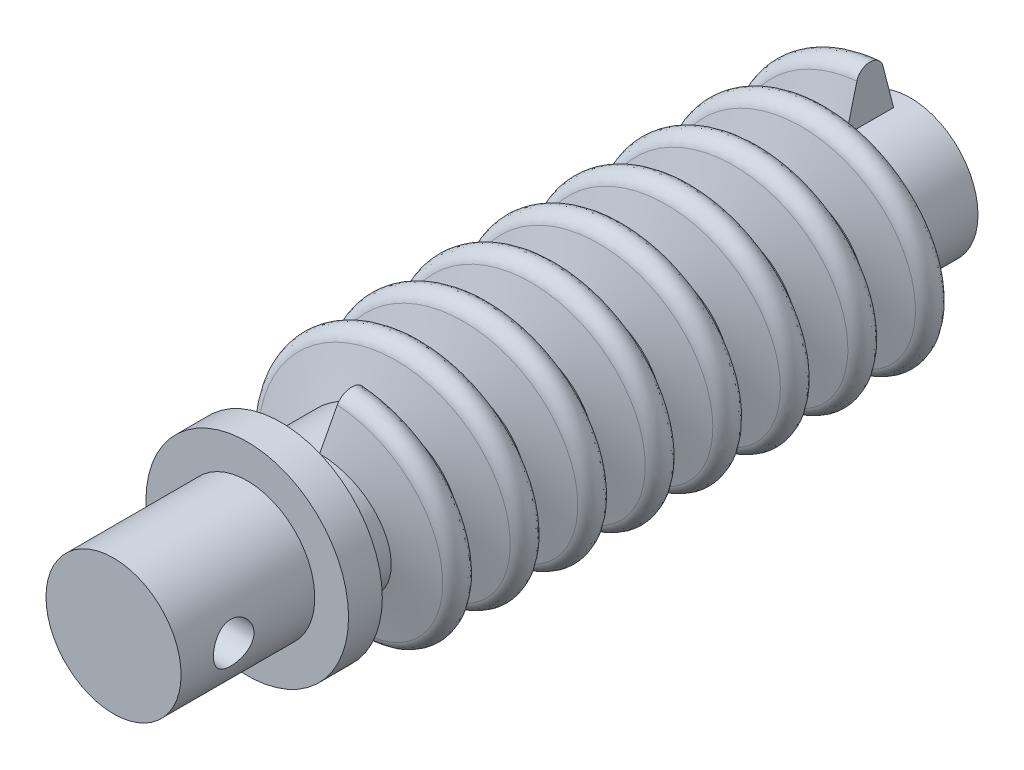
SolidWorks part; units mm, degrees
ref_plane "Front Plane" through (0, 0, 0) normal (0, 0, 1) x (1, 0, 0)
ref_plane "Top Plane" through (0, 0, 0) normal (0, 1, 0) x (1, 0, 0)
ref_plane "Right Plane" through (0, 0, 0) normal (1, 0, 0) x (0, 0, -1)
sketch "Sketch2" plane through (0, 0, 0) normal (0, 0, 1) x (1, 0, 0)
  circle A0 centre (0, 0) radius 5
  dimension "D1" = 10
extrude "Boss-Extrude1" add sketch "Sketch2" along normal blind 38
sketch "Sketch3" plane through (0, 0, 38) normal (0, 0, 1) x (1, 0, 0)
  circle A0 centre (0, 0) radius 5 construction
  circle A1 centre (0, 0) radius 5
curve "Helix/Spiral1" pitch 5 height 40 radius 5 centre (0, 0, 38) axis (0, 0, -1) start towards (0, 1, 0)
sketch "Sketch4" plane through (0, 0, 38) normal (0, 0, 1) x (1, 0, 0)
  circle A1 centre (0, 0) radius 5
  circle A2 centre (0, 0) radius 5
  dimension "D1" = 0
sketch "Sketch6" plane through (0, 0, 38) normal (0, 0, 1) x (1, 0, 0)
  circle A1 centre (0, 0) radius 5
  circle A2 centre (0, 0) radius 5
  dimension "D1" = 0
extrude "Boss-Extrude3" add sketch "Sketch6" along normal blind 16 and the other way blind 43
sketch "Sketch7" plane through (0, 0, 0) normal (1, 0, 0) x (0, 0, -1)
  line L0 (-38, 5) -> (-38, 7.8) construction
  line L1 (5, 5) -> (-54, 5) construction
  line L2 (-39.75, 5) -> (-38.9687, 8.0483)
  line L3 (-36.25, 5) -> (-37.0313, 8.0483)
  line L4 (-39.75, 5) -> (-39.75, 4.2924)
  line L5 (-39.75, 4.2924) -> (-36.25, 4.2924)
  line L6 (-36.25, 4.2924) -> (-36.25, 5)
  arc A0 (-38.9687, 8.0483) -> (-37.0313, 8.0483) centre (-38, 7.8) cw
  spline S0 degree 3 poles (-38, 5) (-37.8965, 5) (-37.6872, 4.7397) (-37.3751, 3.6276) (-37.0625, 1.9632) (-36.75, 0) (-36.4375, -1.9632) (-36.125, -3.6276) (-35.8125, -4.7397) (-35.5, -5.1302) (-35.1875, -4.7397) (-34.875, -3.6276) (-34.4583, -1.4084) (-34.0417, 1.4084) (-33.625, 3.6276) (-33.3125, 4.7397) (-33, 5.1302) (-32.6875, 4.7397) (-32.375, 3.6276) (-31.9583, 1.4084) (-31.5417, -1.4084) (-31.125, -3.6276) (-30.8125, -4.7397) (-30.5, -5.1302) (-30.1875, -4.7397) (-29.875, -3.6276) (-29.4583, -1.4084) (-29.0417, 1.4084) (-28.625, 3.6276) (-28.3125, 4.7397) (-28, 5.1302) (-27.6875, 4.7397) (-27.375, 3.6276) (-26.9583, 1.4084) (-26.5417, -1.4084) (-26.125, -3.6276) (-25.8125, -4.7397) (-25.5, -5.1302) (-25.1875, -4.7397) (-24.875, -3.6276) (-24.4583, -1.4084) (-24.0417, 1.4084) (-23.625, 3.6276) (-23.3125, 4.7397) (-23, 5.1302) (-22.6875, 4.7397) (-22.375, 3.6276) (-21.9583, 1.4084) (-21.5417, -1.4084) (-21.125, -3.6276) (-20.8125, -4.7397) (-20.5, -5.1302) (-20.1875, -4.7397) (-19.875, -3.6276) (-19.4583, -1.4084) (-19.0417, 1.4084) (-18.625, 3.6276) (-18.3125, 4.7397) (-18, 5.1302) (-17.6875, 4.7397) (-17.375, 3.6276) (-16.9583, 1.4084) (-16.5417, -1.4084) (-16.125, -3.6276) (-15.8125, -4.7397) (-15.5, -5.1302) (-15.1875, -4.7397) (-14.875, -3.6276) (-14.4583, -1.4084) (-14.0417, 1.4084) (-13.625, 3.6276) (-13.3125, 4.7397) (-13, 5.1302) (-12.6875, 4.7397) (-12.375, 3.6276) (-11.9583, 1.4084) (-11.5417, -1.4084) (-11.125, -3.6276) (-10.8125, -4.7397) (-10.5, -5.1302) (-10.1875, -4.7397) (-9.875, -3.6276) (-9.4583, -1.4084) (-9.0417, 1.4084) (-8.625, 3.6276) (-8.3125, 4.7397) (-8, 5.1302) (-7.6875, 4.7397) (-7.375, 3.6276) (-6.9583, 1.4084) (-6.5417, -1.4084) (-6.125, -3.6276) (-5.8125, -4.7397) (-5.5, -5.1302) (-5.1875, -4.7397) (-4.875, -3.6276) (-4.4583, -1.4084) (-4.0417, 1.4084) (-3.625, 3.6276) (-3.3125, 4.7397) (-3, 5.1302) (-2.6875, 4.7397) (-2.375, 3.6276) (-1.9583, 1.4084) (-1.5417, -1.4084) (-1.125, -3.6276) (-0.8125, -4.7397) (-0.5, -5.1302) (-0.1875, -4.7397) (0.125, -3.6276) (0.4375, -1.9632) (0.75, 0) (1.0625, 1.9632) (1.3751, 3.6276) (1.6872, 4.7397) (1.8965, 5) (2, 5) knots 0 0 0 0 0.007813 0.015625 0.023438 0.03125 0.039063 0.046875 0.054688 0.0625 0.070313 0.078125 0.085938 0.101563 0.109375 0.117188 0.125 0.132813 0.140625 0.148438 0.164063 0.171875 0.179688 0.1875 0.195313 0.203125 0.210938 0.226563 0.234375 0.242188 0.25 0.257813 0.265625 0.273438 0.289063 0.296875 0.304688 0.3125 0.320313 0.328125 0.335938 0.351563 0.359375 0.367188 0.375 0.382813 0.390625 0.398438 0.414063 0.421875 0.429688 0.4375 0.445313 0.453125 0.460938 0.476563 0.484375 0.492188 0.5 0.507813 0.515625 0.523438 0.539063 0.546875 0.554688 0.5625 0.570313 0.578125 0.585938 0.601563 0.609375 0.617188 0.625 0.632813 0.640625 0.648438 0.664063 0.671875 0.679688 0.6875 0.695313 0.703125 0.710938 0.726563 0.734375 0.742188 0.75 0.757813 0.765625 0.773438 0.789063 0.796875 0.804688 0.8125 0.820313 0.828125 0.835938 0.851563 0.859375 0.867188 0.875 0.882813 0.890625 0.898438 0.914063 0.921875 0.929688 0.9375 0.945313 0.953125 0.960938 0.96875 0.976562 0.984375 0.992188 1 1 1 1 construction
  dimension "D3" = 1
  dimension "D1" = 2.8
  dimension "D2" = 3.5
sweep "Sweep1" add profiles "Sketch7" path "Helix/Spiral1"
draft "Draft4" type of draft neutral plane draft angle 10 neutral plane "Top Plane" faces to draft 1 face at (0, 6.7121, 38) neutral plane through (0, 0, 0) neutral plane normal (0, 1, 0) parameters "D1"=10
sketch "Sketch9" plane through (0, 0, 0) normal (1, 0, 0) x (0, 0, -1)
  line L0 (-44.1011, -20.3711) -> (-44.1011, -27.5737) construction
  line L1 (-44.1011, 4.0205) -> (-41.6011, 4.0205)
  line L2 (-44.1011, 4.0205) -> (-44.1011, 7.5)
  line L3 (-44.1011, 7.5) -> (-41.6011, 7.5)
  line L4 (-41.6011, 4.0205) -> (-41.6011, 7.5)
  line L5 (-34.75, 5) -> (-54, 5) construction
  line L6 (-54, 0) -> (-49.6548, 0) construction
  line L7 (-54, 5) -> (-54, -5) construction
  dimension "D1" = 2.5
  dimension "D2" = 2.5
revolve "Revolve1" add sketch "Sketch9" angle 360 about L6
sketch "Sketch12" plane through (0, 0, 0) normal (1, 0, 0) x (0, 0, -1)
  line L0 (-54, 0) -> (-47.1832, 0) construction
  line L1 (-54, 5) -> (-54, -5) construction
  line L2 (-44.1011, 7.5) -> (-44.1011, -7.5) construction
  circle A0 centre (-50.1011, 0) radius 1.5
  dimension "D2" = 3
  dimension "D1" = 6
extrude "Cut-Extrude1" cut sketch "Sketch12" against normal through all both and the other way through all
